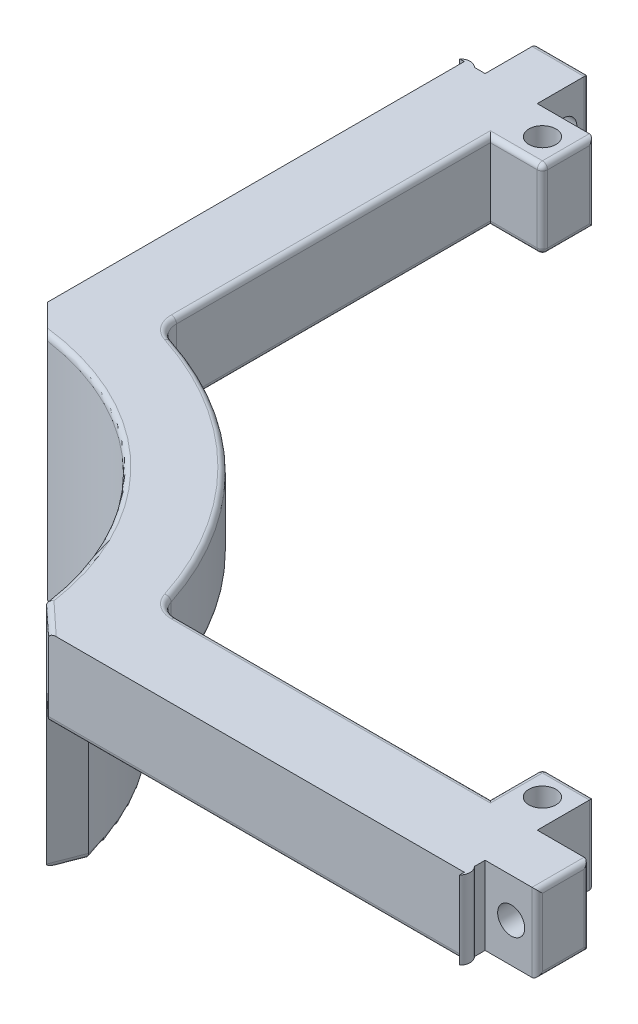
SolidWorks part; units mm, degrees
ref_plane "Front Plane" through (0, 0, 0) normal (0, 0, 1) x (1, 0, 0)
ref_plane "Top Plane" through (0, 0, 0) normal (0, 1, 0) x (1, 0, 0)
ref_plane "Right Plane" through (0, 0, 0) normal (1, 0, 0) x (0, 0, -1)
sketch "Sketch1" plane through (0, 0, 0) normal (0, 1, 0) x (1, 0, 0)
  line L2 (0, 0) -> (0, -107.95)
  line L3 (-2.3808, -173.5658) -> (164.9741, -6.2109) construction
  line L8 (31.75, 0) -> (31.75, -12.7)
  line L9 (31.75, -12.7) -> (19.05, -12.7)
  line L10 (19.05, -12.7) -> (19.05, -93.012)
  line L12 (158.485, -152.135) -> (78.173, -152.135)
  line L13 (158.485, -139.435) -> (158.485, -152.135)
  line L14 (171.185, -139.435) -> (158.485, -139.435)
  line L21 (171.185, -171.185) -> (63.235, -171.185)
  line L26 (2.54, 0) -> (-1.143, 2.54)
  line L27 (-1.143, 2.54) -> (-1.143, 0)
  line L28 (-1.143, 0) -> (0, 0)
  line L29 (171.185, -139.435) -> (171.185, -168.645)
  line L30 (171.185, -168.645) -> (173.725, -172.328)
  line L31 (173.725, -172.328) -> (171.185, -172.328)
  line L32 (171.185, -172.328) -> (171.185, -171.185)
  line L33 (2.54, 0) -> (31.75, 0)
  arc A0 (0, -107.95) -> (63.235, -171.185) centre (-2.3808, -173.5658) cw
  arc A1 (19.05, -93.012) -> (78.173, -152.135) centre (-3.1739, -174.3589) cw
  circle A2 centre (25.4, -6.35) radius 3.302
  circle A3 centre (164.835, -145.785) radius 3.302
  dimension "D4" = 65.659
  dimension "D5" = 87.4831
  dimension "D7" = 84.328
  dimension "D15" = 6.604
  dimension "D3" = 98.3742
  dimension "D8" = 6.35
  dimension "D2" = 45
  dimension "D6" = 19.05
  dimension "D9" = 2.54
  dimension "D10" = 1.143
  dimension "D11" = 2.54
  dimension "D12" = 1.143
  dimension "D13" = 12.7
  dimension "D14" = 12.7
  dimension "D16" = 2.54
  dimension "D17" = 6.35
  dimension "D18" = 107.95
  dimension "D19" = 2.54
extrude "Boss-Extrude1" add sketch "Sketch1" along normal blind 19.05
chamfer "Chamfer1" distance 6.35 angle 45 2 edges at (63.235, 9.525, 171.185) (0, 9.525, 107.95)
fillet "Fillet1" radius 5.08 2 edges at (78.173, 9.525, 152.135) (19.05, 9.525, 93.012)
fillet "Fillet2" radius 1.27 24 edges at (120.224, 0, 152.135) (78.9692, 0, 151.1591) (19.05, 0, 50.961) (20.0259, 0, 92.2158) (120.224, 19.05, 152.135) (78.9692, 19.05, 151.1591) (19.05, 19.05, 50.961) (20.0259, 19.05, 92.2158) (158.485, 0, 145.785) (164.835, 0, 139.435) (158.485, 9.525, 139.435) (31.75, 0, 6.35) (31.75, 9.525, 12.7) (31.75, 19.05, 6.35) (25.4, 19.05, 12.7) (25.4, 0, 12.7) (164.835, 19.05, 139.435) (158.485, 19.05, 145.785) (66.2395, 19.05, 167.8474) (44.1548, 19.05, 127.2459) (56.455, 0, 114.73) (56.455, 19.05, 114.73) (171.185, 9.525, 139.435) (31.75, 9.525, 0)
fillet "Fillet3" radius 1.27 1 edges at (120.5067, 0, 171.185)
sketch "Sketch4" plane through (19.05, 0, 0) normal (1, 0, 0) x (0, 0, -1)
  line L0 (-12.7, 17.78) -> (-12.7, 1.27) construction
  circle A0 centre (-19.05, 9.525) radius 3.302
  point P4 (-12.7, 9.525)
  dimension "D2" = 6.604
  dimension "D1" = 6.35
extrude "Cut-Extrude3" [suppressed] cut sketch "Sketch4" against normal up to next
sketch "Sketch5" plane through (0, 0, 152.135) normal (0, 0, -1) x (-1, 0, 0)
  line L0 (-158.485, 17.78) -> (-158.485, 1.27) construction
  circle A0 centre (-152.135, 9.525) radius 3.302
  point P4 (-158.485, 9.525)
  dimension "D1" = 6.604
  dimension "D2" = 6.35
extrude "Cut-Extrude4" [suppressed] cut sketch "Sketch5" against normal up to next
sketch "Sketch6" plane through (0, 0, 0) normal (0, -1, 0) x (1, 0, 0)
  line L12 (6.9771, 108.5771) -> (14.3764, 105.7557)
  line L13 (62.6506, 164.5099) -> (65.5064, 157.1238)
  arc A1 (14.3764, 105.7557) -> (65.5064, 157.1238) centre (-2.3808, 173.5658) ccw
  arc A2 (6.9771, 108.5771) -> (62.6506, 164.5099) centre (-2.3808, 173.5658) ccw construction
  arc A3 (62.6506, 164.5099) -> (6.9771, 108.5771) centre (-2.3808, 173.5658) cw
  dimension "D1" = 69.85
  dimension "D2" = 76.2
extrude "Boss-Extrude2" add sketch "Sketch6" along normal blind 38.1
fillet "Fillet5" radius 2.54 2 edges at (173.725, 9.525, 172.328) (-1.143, 9.525, -2.54)
fillet "Fillet6" radius 1.27 4 edges at (64.0785, -38.1, 160.8168) (10.6768, -38.1, 107.1664) (47.1252, -38.1, 124.2893) (44.1548, -38.1, 127.2459)
sketch "Sketch7" plane through (0, 0, 0) normal (0, 0, -1) x (-1, 0, 0)
  line L0 (-30.48, 19.05) -> (-30.48, 0) construction
  line L1 (-17.78, 19.05) -> (-5.08, 19.05)
  line L2 (-17.78, 19.05) -> (-17.78, 0)
  line L3 (-17.78, 0) -> (-5.08, 0)
  line L4 (-5.08, 19.05) -> (-5.08, 0)
  point P6 (-17.78, 9.525)
  point P7 (-30.48, 9.525)
  dimension "D1" = 12.7
  dimension "D2" = 19.05
  dimension "D3" = 12.7
extrude "Boss-Extrude3" add sketch "Sketch7" along normal blind 12.7
sketch "Sketch8" plane through (5.08, 0, 0) normal (-1, 0, 0) x (0, 0, 1)
  line L0 (-12.7, 19.05) -> (0, 19.05) construction
  line L1 (-12.7, 0) -> (-12.7, 19.05) construction
  circle A0 centre (-6.35, 9.525) radius 3.302
  point P4 (-6.35, 19.05)
  point P7 (-12.7, 9.525)
  dimension "D1" = 6.604
extrude "Cut-Extrude5" cut sketch "Sketch8" against normal up to next
sketch "Sketch9" plane through (171.185, 0, -171.185) normal (-1, 0, 0) x (0, 0, 1)
  line L1 (324.59, 19.05) -> (337.29, 19.05)
  line L2 (324.59, 19.05) -> (324.59, 0)
  line L3 (324.59, 0) -> (337.29, 0)
  line L4 (337.29, 19.05) -> (337.29, 0)
  line L5 (311.89, 0) -> (311.89, 19.05) construction
  point P6 (311.89, 9.525)
  point P7 (324.59, 9.525)
  dimension "D1" = 12.7
  dimension "D2" = 19.05
  dimension "D3" = 12.7
extrude "Boss-Extrude4" add sketch "Sketch9" against normal blind 12.7
sketch "Sketch10" plane through (0, 0, 166.105) normal (0, 0, 1) x (1, 0, 0)
  line L0 (183.885, 19.05) -> (171.185, 19.05) construction
  line L1 (183.885, 0) -> (183.885, 19.05) construction
  circle A0 centre (177.535, 9.525) radius 3.302
  point P4 (177.535, 19.05)
  point P7 (183.885, 9.525)
  dimension "D1" = 6.604
extrude "Cut-Extrude6" cut sketch "Sketch10" against normal up to next
fillet "Fillet7" radius 1.27 8 edges at (183.885, 0, 159.755) (183.885, 9.525, 166.105) (183.885, 19.05, 159.755) (183.885, 9.525, 153.405) (11.43, 19.05, -12.7) (5.08, 9.525, -12.7) (11.43, 0, -12.7) (17.78, 9.525, -12.7)
